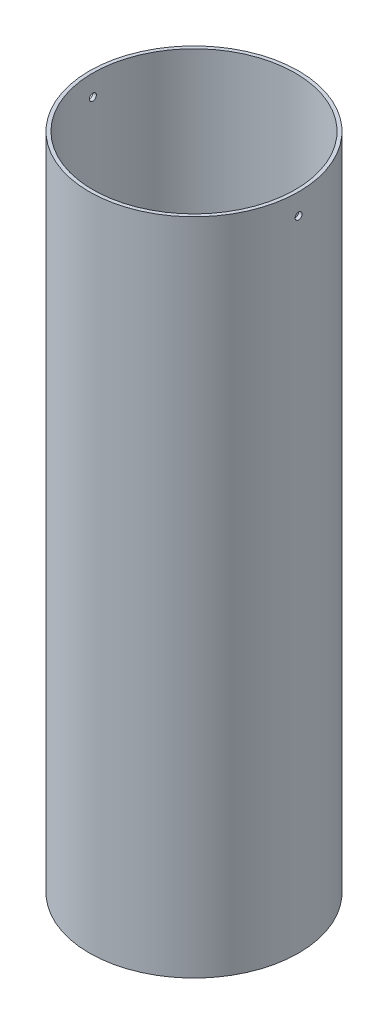
SolidWorks part; units mm, degrees
material "PC High Viscosity"
ref_plane "Front Plane" through (0, 0, 0) normal (0, 0, 1) x (1, 0, 0)
ref_plane "Top Plane" through (0, 0, 0) normal (0, 1, 0) x (1, 0, 0)
ref_plane "Right Plane" through (0, 0, 0) normal (1, 0, 0) x (0, 0, -1)
sketch "Sketch1" plane through (0, 0, 0) normal (0, 0, 1) x (1, 0, 0)
  line L0 (0, 0) -> (0, 600) construction
  line L1 (95.25, 0) -> (92.075, 0)
  line L2 (95.25, 600) -> (95.25, 0)
  line L3 (92.075, 0) -> (92.075, 600)
  line L4 (92.075, 600) -> (95.25, 600)
  line L5 (0, 600) -> (92.075, 600) construction
  line L6 (0, 0) -> (92.075, 0) construction
  dimension "D1" = 92.075
  dimension "D2" = 3.175
  dimension "D3" = 600
revolve "Revolve1" add sketch "Sketch1" angle 360 about L0
ref_plane "Plane1" through (0, 0, 101) normal (0, 0, 1) x (1, 0, 0)
ref_plane "Plane2" through (95.25, 0, 0) normal (1, 0, 0) x (0, 0, -1)
sketch "Sketch3" plane through (95.25, 0, 0) normal (1, 0, 0) x (0, 0, -1)
  line L0 (92.075, 600) -> (-92.075, 600) construction
  circle A0 centre (0, 580.95) radius 3.175
  dimension "D1" = 19.05
  dimension "D2" = 6.35
extrude "Cut-Extrude1" cut sketch "Sketch3" against normal up to surface (3.2298 mm away) up to face at (0, 0, -92.075)
pattern_circular "CirPattern1" count 2 every 180 about axis through (0, 600, 0) along (0, -1, 0) of "Cut-Extrude1"
